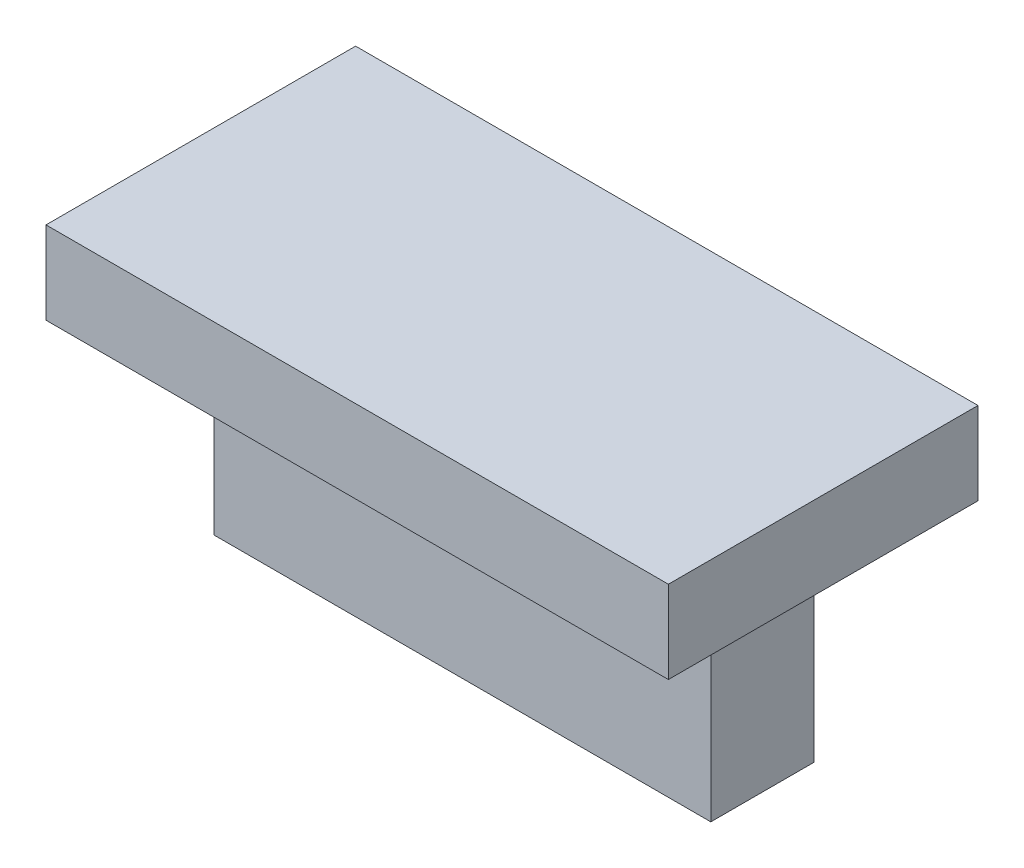
SolidWorks part; units mm, degrees
material "Acrylic (Medium-high impact)"
ref_plane "Front Plane" through (0, 0, 0) normal (0, 0, 1) x (1, 0, 0)
ref_plane "Top Plane" through (0, 0, 0) normal (0, 1, 0) x (1, 0, 0)
ref_plane "Right Plane" through (0, 0, 0) normal (1, 0, 0) x (0, 0, -1)
sketch "Sketch2" plane through (0, 0, 0) normal (0, 0, 1) x (1, 0, 0)
  line L6 (-13.6717, 6.1769) -> (-13.6717, -20.5896)
  line L14 (-13.6717, -20.5896) -> (47.4401, -20.5896)
  line L15 (47.4401, -20.5896) -> (47.4401, 6.1769)
  line L19 (-13.6717, 6.1769) -> (-13.6717, 7.7521)
  line L20 (-13.6717, 7.7521) -> (47.4401, 7.7521)
  line L21 (47.4401, 6.1769) -> (47.4401, 7.7521)
  line L22 (-21.6699, 14.8266) -> (54.9183, 14.8266)
  line L23 (-21.6699, 14.8266) -> (-21.6699, 4.6666)
  line L24 (-21.6699, 4.6666) -> (54.9183, 4.6666)
  line L25 (54.9183, 14.8266) -> (54.9183, 4.6666)
  circle A1 centre (0, 0) radius 3.3131
  circle A2 centre (38.1, 0) radius 3.3131
  dimension "D1" = 10.16
extrude "Boss-Extrude6" add sketch "Sketch2" along normal mid plane 12.7 contours L24 L6 L14 L15 A1 A2 region at (16.7829, -8.3339, 0)
extrude "Boss-Extrude7" add sketch "Sketch2<5>" along normal mid plane 38.1 contours L22 L25 L24 L23
sketch "Sketch2<5>" plane through (0, 0, 0) normal (0, 0, 1) x (1, 0, 0) same geometry as "Sketch2"
